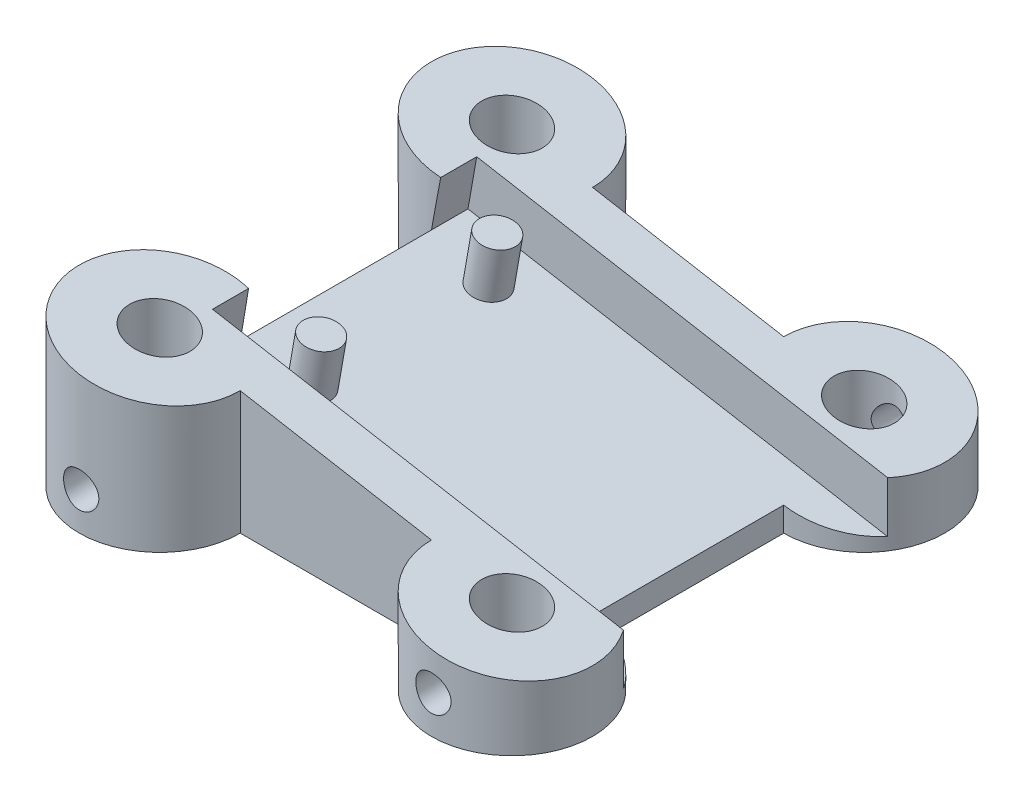
SolidWorks part; units mm, degrees
ref_plane "Front Plane" through (0, 0, 0) normal (0, 0, 1) x (1, 0, 0)
ref_plane "Top Plane" through (0, 0, 0) normal (0, 1, 0) x (1, 0, 0)
ref_plane "Right Plane" through (0, 0, 0) normal (1, 0, 0) x (0, 0, -1)
sketch "Sketch1" plane through (0, 0, 0) normal (0, 1, 0) x (1, 0, 0)
  line L0 (14, 28) -> (14, 0) construction
  line L1 (0, 0) -> (28, 0)
  line L2 (0, 0) -> (0, 28)
  line L3 (0, 28) -> (28, 28)
  line L4 (28, 0) -> (28, 28)
  line L5 (0, 14) -> (28, 14) construction
  point P9 (14, 14)
  dimension "D1" = 28
extrude "Boss-Extrude1" add sketch "Sketch1" along normal blind 10.9372
sketch "Sketch2" plane through (0, 0, 0) normal (0, 0, 1) x (1, 0, 0)
  line L0 (0, 10.9372) -> (28, 6)
  line L1 (0, 10.9372) -> (28, 10.9372) construction
  line L2 (28, 10.9372) -> (28, 0) construction
  line L3 (0, 10.9372) -> (28, 10.9372)
  line L4 (28, 10.9372) -> (28, 6)
  dimension "D2" = 6
  dimension "D3" = 10
extrude "Cut-Extrude1" cut sketch "Sketch2" against normal through all
sketch "Sketch3" plane through (1.8704, 10.6074, 0) normal (0.1736, 0.9848, 0) x (0.9848, -0.1736, 0)
  line L0 (-1.8992, 28) -> (-1.8992, 0) construction
  line L1 (-1.8992, 3.5) -> (48.1008, 3.5)
  line L2 (-1.8992, 3.5) -> (-1.8992, 24.5)
  line L3 (-1.8992, 24.5) -> (48.1008, 24.5)
  line L4 (48.1008, 3.5) -> (48.1008, 24.5)
  point P9 (-1.8992, 14)
  point P10 (-1.8992, 14)
  dimension "D1" = 21
  dimension "D2" = 50
extrude "Cut-Extrude2" cut sketch "Sketch3" against normal blind 4
ref_plane "Plane1" through (0, 10.9372, 0) normal (0, 1, 0) x (1, 0, 0)
sketch "Sketch11" plane through (1.1758, 6.6681, 0) normal (0.1736, 0.9848, 0) x (0.9848, -0.1736, 0)
  line L0 (27.238, 24.5) -> (-1.1939, 24.5) construction
  line L1 (27.238, 24.5) -> (27.238, 3.5) construction
  line L2 (-1.1939, 3.5) -> (27.238, 3.5) construction
  line L3 (27.238, 24.5) -> (-1.1939, 24.5) construction
  line L4 (27.238, 24.5) -> (27.238, 3.5) construction
  line L5 (-1.1939, 3.5) -> (27.238, 3.5) construction
  line L6 (13.0221, 3) -> (13.0221, 50003) construction
  line L7 (24.633, 14) -> (-49975.367, 14) construction
  circle A2 centre (4.0221, 21) radius 1.45
  circle A3 centre (4.0221, 7) radius 1.45
  point P6 (13.0221, 3.5)
  point P9 (27.238, 14)
  dimension "D4" = 2.9
  dimension "D5" = 9
  dimension "D6" = 7
extrude "Boss-Extrude2" add sketch "Sketch11" along normal blind 4
sketch "Sketch12" plane through (0, 10.9372, 0) normal (0, 1, 0) x (1, 0, 0)
  line L0 (0, 3.5) -> (0, 24.5) construction
  line L1 (0, 3.5) -> (28, 3.5) construction
  line L2 (0, 3.5) -> (0, 24.5) construction
  line L3 (0, 3.5) -> (28, 3.5) construction
  line L4 (0, 14) -> (50000, 14) construction
  line L5 (14, 4) -> (14, 50004) construction
  circle A0 centre (14, 14) radius 7
  point P7 (0, 14)
  point P10 (14, 3.5)
  dimension "D1" = 14
sketch "Sketch13" plane through (0, 0, 0) normal (0, -1, 0) x (1, 0, 0)
  line L0 (0, 0) -> (28, 0) construction
  line L1 (28, 0) -> (28, -28) construction
  line L2 (28, -28) -> (0, -28) construction
  line L3 (0, -28) -> (0, 0) construction
  line L4 (0, 0) -> (28, 0) construction
  line L5 (28, 0) -> (28, -28) construction
  line L6 (28, -28) -> (0, -28) construction
  line L7 (0, -28) -> (0, 0) construction
  line L8 (0, -14) -> (28, -14) construction
  line L9 (14, -28) -> (14, 0) construction
  circle A0 centre (0, 0) radius 2.4
  circle A1 centre (28, 0) radius 2.4
  circle A2 centre (28, -28) radius 2.4
  circle A3 centre (0, -28) radius 2.4
  dimension "D1" = 4.8
  dimension "D2" = 2
  dimension "D3" = 2
extrude "Cut-Extrude5" cut sketch "Sketch13" against normal through all
sketch "Sketch14" plane through (0, 0, 0) normal (0, -1, 0) x (1, 0, 0)
  line L0 (28, -3.5) -> (28, -2.4) construction
  line L1 (2.4, -28) -> (25.6, -28) construction
  line L2 (0, -3.5) -> (0, -24.5) construction
  circle A0 centre (0, 0) radius 2.4 construction
  circle A1 centre (0, 0) radius 2.4 construction
  circle A2 centre (0, 0) radius 6.4
  circle A3 centre (0, 0) radius 2.4
  circle A4 centre (28, 0) radius 2.4
  circle A5 centre (28, 0) radius 6.4
  circle A6 centre (28, -28) radius 2.4
  circle A7 centre (28, -28) radius 6.4
  circle A8 centre (0, -28) radius 2.4
  circle A9 centre (0, -28) radius 6.4
  dimension "D1" = 4
  dimension "D4" = 4.8
  dimension "D2" = 2
  dimension "D3" = 2
extrude "Boss-Extrude3" add sketch "Sketch14" against normal up to surface (10.9372 mm away) up to face at (14, 8.4686, -25.8676)
sketch "Sketch15" plane through (0, 0, -28) normal (0, 0, -1) x (-1, 0, 0)
  line L0 (-21.6, 0) -> (-6.4, 0) construction
  line L1 (-21.9, 0) -> (-0.9, 0) construction
  line L4 (-14, 8.4686) -> (-14, 0) construction
  line L5 (-6.4, 9.8087) -> (-21.6, 7.1285) construction
  circle A0 centre (-28, 3) radius 1.4
  circle A1 centre (0, 3) radius 1.4
  point P4 (-28, 0)
  dimension "D1" = 2.8
  dimension "D2" = 3
extrude "Cut-Extrude6" cut sketch "Sketch15" along normal through all
sketch "Sketch16" plane through (0, 0, 0) normal (0, 0, 1) x (1, 0, 0)
  circle A0 centre (0, 3) radius 1.4 construction
  circle A1 centre (28, 3) radius 1.4 construction
  circle A2 centre (0, 3) radius 1.4
  circle A3 centre (28, 3) radius 1.4
extrude "Cut-Extrude7" cut sketch "Sketch16" along normal through all
sketch "Sketch18" plane through (1.8704, 10.6074, 0) normal (0.1736, 0.9848, 0) x (0.9848, -0.1736, 0)
  line L5 (-1.8992, 3.5) -> (25.6754, 3.5) construction
  line L8 (3.5416, 3.5) -> (21.0919, 3.5) construction
  line L9 (3.5416, 3.5) -> (21.0919, 3.5) construction
  line L22 (4.2469, 24.5) -> (-1.1939, 24.5)
  line L37 (6.0919, 3.5) -> (36.0919, 3.5)
  line L38 (6.0919, 3.5) -> (6.0919, 24.5)
  line L39 (6.0919, 24.5) -> (36.0919, 24.5)
  line L40 (36.0919, 3.5) -> (36.0919, 24.5)
  line L42 (-1.1939, 24.5) -> (-1.1939, 21.6)
  line L46 (-1.1939, 6.4) -> (-1.1939, 3.5)
  line L47 (-1.1939, 3.5) -> (4.2469, 3.5)
  line L49 (3.5416, 24.5) -> (21.0919, 24.5) construction
  ellipse E1 centre (-1.1939, 28) end of major axis (5.3048, 28) minor radius 6.4 (-1.1939, 21.6) -> (4.2469, 24.5) ccw construction
  ellipse E2 centre (-1.1939, 28) end of major axis (5.3048, 28) minor radius 6.4 (-1.1939, 21.6) -> (4.2469, 24.5) ccw
  ellipse E3 centre (-1.1939, 0) end of major axis (-7.6926, 0) minor radius 6.4 (4.2469, 3.5) -> (-1.1939, 6.4) ccw construction
  ellipse E4 centre (-1.1939, 0) end of major axis (5.3048, 0) minor radius 6.4 (4.2469, 3.5) -> (-1.1939, 6.4) ccw
  point P7 (21.0919, 3.5)
  dimension "D1" = 30
extrude "Cut-Extrude8" cut sketch "Sketch18" against normal up to surface (4 mm away) up to face at (6.5647, 5.7179, -21)
equation "\"TrackLength\"= 150"
equation "\"MarbleWidth\"= 13"
equation "\"MarbleTrackWidth\"= \"MarbleWidth\" - 1"
equation "\"TrackWidth\"= \"MarbleTrackWidth\" + ( 2 * 4 )"
equation "\"MarbleTrackLength\"= \"TrackLength\" - ( 2 * 8 )"
equation "\"MountWidth\"= \"TrackWidth\" + 8"
equation "\"D1@Sketch1\"=\"MountWidth\""
equation "\"D1@Boss-Extrude1\"=\"RampHeight\""
equation "\"RampDepth\"=6"
equation "\"RampAngle\"= 10"
equation "\"RampHeight\"= ( \"MountWidth\" * tan ( \"RampAngle\" ) ) + \"RampDepth\""
equation "\"D1@Sketch3\"=\"TrackWidth\" + 1"
equation "\"MountWidth\"= \"TrackWidth\" + 10"
equation "\"MountLength\"=66.6651"
